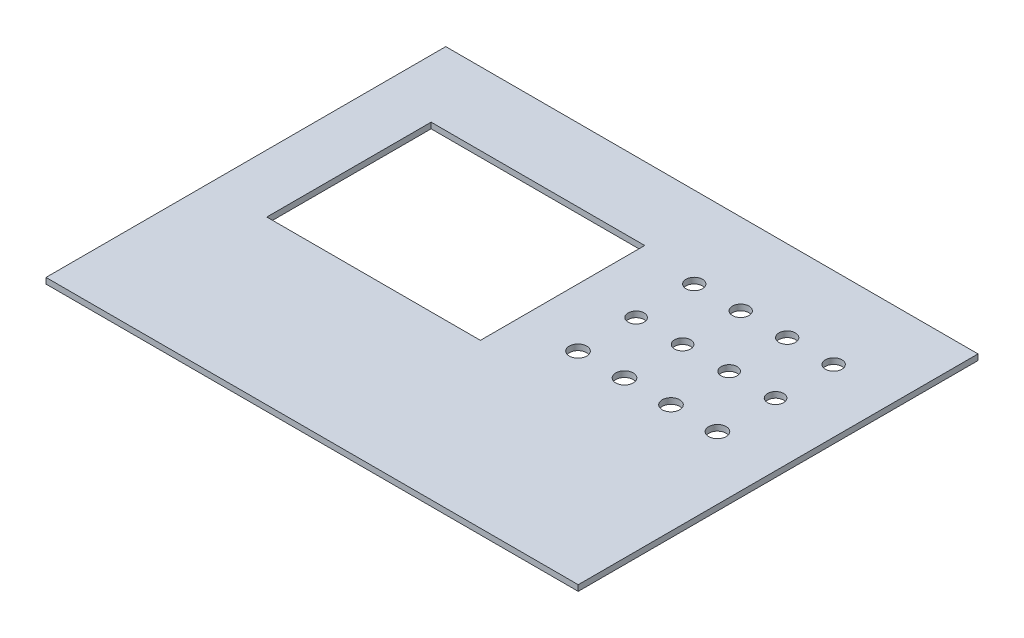
SolidWorks part; units mm, degrees
ref_plane "Front Plane" through (0, 0, 0) normal (0, 0, 1) x (1, 0, 0)
ref_plane "Top Plane" through (0, 0, 0) normal (0, 1, 0) x (1, 0, 0)
ref_plane "Right Plane" through (0, 0, 0) normal (1, 0, 0) x (0, 0, -1)
sketch "Sketch1" plane through (0, 0, 0) normal (0, 1, 0) x (1, 0, 0)
  line L1 (0, 0) -> (581.66, 0)
  line L2 (0, 0) -> (0, 436.88)
  line L3 (0, 436.88) -> (581.66, 436.88)
  line L4 (581.66, 0) -> (581.66, 436.88)
  dimension "D1" = 581.66
  dimension "D2" = 436.88
extrude "Boss-Extrude1" add sketch "Sketch1" along normal blind 6.35
sketch "Sketch3" plane through (0, 6.35, 0) normal (0, 1, 0) x (1, 0, 0)
  line L0 (0, 0) -> (581.66, 0) construction
  line L1 (63.5, 357.378) -> (296.926, 357.378)
  line L2 (63.5, 357.378) -> (63.5, 177.8)
  line L3 (63.5, 177.8) -> (296.926, 177.8)
  line L4 (296.926, 357.378) -> (296.926, 177.8)
  line L5 (0, 436.88) -> (0, 0) construction
  point P4 (180.213, 177.8)
  point P7 (63.5, 267.589)
  dimension "D1" = 233.426
  dimension "D2" = 179.578
  dimension "D3" = 177.8
  dimension "D4" = 63.5
extrude "Cut-Extrude2" cut sketch "Sketch3" against normal through all
sketch "Sketch4" plane through (0, 6.35, 0) normal (0, 1, 0) x (1, 0, 0)
  line L0 (296.926, 177.8) -> (296.926, 357.378) construction
  line L1 (581.66, 436.88) -> (0, 436.88) construction
  circle A0 centre (360.426, 347.98) radius 9.017
  circle A1 centre (411.226, 347.98) radius 9.017
  circle A2 centre (462.026, 347.98) radius 9.017
  circle A3 centre (512.826, 347.98) radius 9.017
  dimension "D1" = 18.034
  dimension "D3" = 63.5
  dimension "D4" = 88.9
  dimension "D5" = 50.8
  dimension "D2" = 4
extrude "Cut-Extrude3" cut sketch "Sketch4" against normal through all
sketch "Sketch5" plane through (0, 6.35, 0) normal (0, 1, 0) x (1, 0, 0)
  line L0 (296.926, 177.8) -> (296.926, 357.378) construction
  line L1 (581.66, 436.88) -> (0, 436.88) construction
  circle A0 centre (360.426, 284.48) radius 8.763
  circle A1 centre (411.226, 284.48) radius 8.763
  circle A2 centre (462.026, 284.48) radius 8.763
  circle A3 centre (512.826, 284.48) radius 8.763
  point P12 (0, 0)
  point P13 (0, 0)
  dimension "D1" = 17.526
  dimension "D3" = 63.5
  dimension "D4" = 152.4
  dimension "D5" = 50.8
  dimension "D2" = 4
extrude "Cut-Extrude4" cut sketch "Sketch5" against normal through all
sketch "Sketch6" plane through (0, 6.35, 0) normal (0, 1, 0) x (1, 0, 0)
  line L0 (296.926, 177.8) -> (296.926, 357.378) construction
  line L1 (581.66, 436.88) -> (0, 436.88) construction
  circle A0 centre (360.426, 220.98) radius 9.525
  circle A1 centre (411.226, 220.98) radius 9.525
  circle A2 centre (462.026, 220.98) radius 9.525
  circle A3 centre (512.826, 220.98) radius 9.525
  dimension "D1" = 19.05
  dimension "D3" = 63.5
  dimension "D4" = 215.9
  dimension "D5" = 50.8
  dimension "D2" = 4
extrude "Cut-Extrude5" cut sketch "Sketch6" against normal through all
